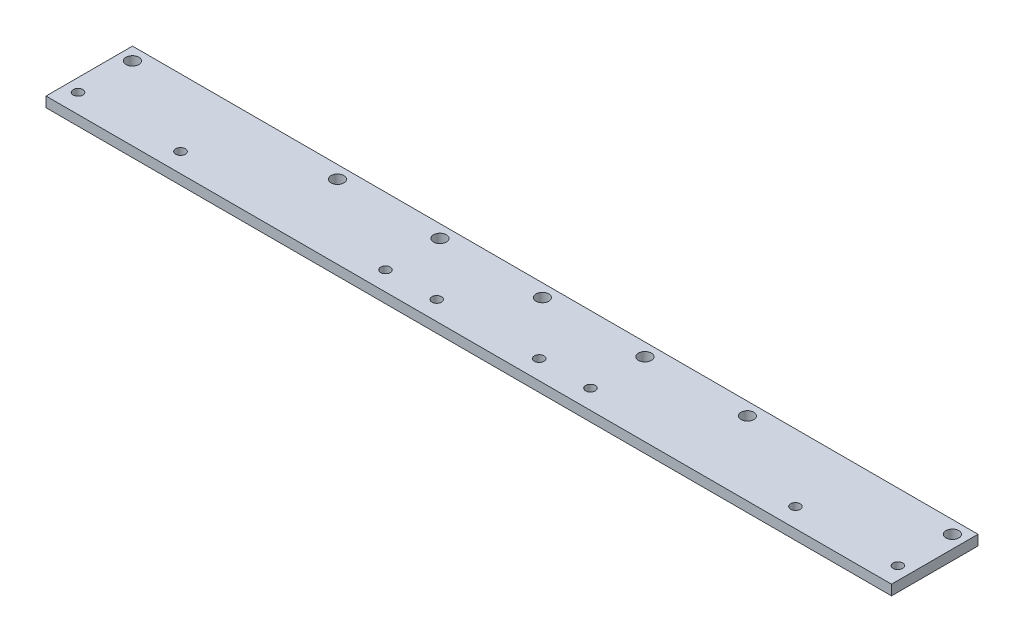
SolidWorks part; units mm, degrees
ref_plane "Front" through (0, 0, 0) normal (0, 0, 1) x (1, 0, 0)
ref_plane "Top" through (0, 0, 0) normal (0, 1, 0) x (1, 0, 0)
ref_plane "Right" through (0, 0, 0) normal (1, 0, 0) x (0, 0, -1)
sketch "Sketch1" plane through (0, 0, 0) normal (0, 1, 0) x (1, 0, 0)
  line L0 (0, 25.5356) -> (0, -1.4644)
  line L3 (0, 25.5356) -> (264, 25.5356)
  line L7 (0, -1.4644) -> (264, -1.4644)
  line L8 (264, -1.4644) -> (264, 25.5356)
  line L9 (264, -1.4644) -> (264, 10.5356)
  line L10 (264, 21.5356) -> (260, 21.5356)
  line L11 (0, 21.5356) -> (4, 21.5356)
  line L12 (4, 21.5356) -> (260, 21.5356)
  line L13 (4, 21.5356) -> (132, 21.5356)
  line L14 (132, 21.5356) -> (260, 21.5356)
  line L15 (264, 10.5356) -> (264, -1.4644)
  line L16 (264, 4.5356) -> (260, 4.5356)
  line L17 (132, 25.5356) -> (132, 23.5356)
  line L18 (4, 21.5356) -> (68, 21.5356)
  line L19 (68, 21.5356) -> (36, 21.5356)
  line L20 (36, 21.5356) -> (36, 4.5356)
  line L21 (196, 21.5356) -> (260, 21.5356)
  line L22 (228, 21.5356) -> (228, 4.5356)
  line L23 (132, 21.5356) -> (132, 4.5356)
  line L24 (132, 21.5356) -> (164, 21.5356)
  circle A0 centre (4, 21.5356) radius 2
  circle A1 centre (260, 21.5356) radius 2
  circle A2 centre (132, 21.5356) radius 2
  circle A3 centre (68, 21.5356) radius 2
  circle A4 centre (196, 21.5356) radius 2
  circle A5 centre (260, 4.5356) radius 1.5
  circle A6 centre (4, 4.5356) radius 1.5
  circle A7 centre (36, 4.5356) radius 1.5
  circle A8 centre (228, 4.5356) radius 1.5
  circle A9 centre (132, 4.5356) radius 1.5
  circle A10 centre (164, 21.5356) radius 2
  circle A11 centre (100, 21.5356) radius 2
  dimension "D5" = 23
  dimension "D6" = 128
  dimension "D9" = 4
  dimension "D10" = 32
  dimension "D1" = 4
  dimension "D2" = 264
  dimension "D3" = 4
  dimension "D4" = 4
  dimension "D7" = 128
  dimension "D8" = 12
extrude "Boss-Extrude1" add sketch "Sketch1" along normal blind 3.175 contours A1 L10 L3 A0 | A1 A0 L10 | A3 L13 A2 L17 L3 L0 L11 A0 | A9 region at (65.9183, 0, -23.5857) region at (1, 0, -18.8856) region at (198.0817, 0, -23.5857)
sketch "Sketch2" plane through (0, 3.175, 0) normal (0, 1, 0) x (1, 0, 0)
  line L0 (37.5, 4.5356) -> (228, 4.5356)
  line L1 (132, 21.5356) -> (132, 4.5356)
  line L2 (132, 4.5356) -> (148, 4.5356)
  line L3 (148, 4.5356) -> (116, 4.5356)
  line L4 (116, 4.5356) -> (100, 4.5356)
  line L5 (148, 4.5356) -> (164, 4.5356)
  circle A0 centre (36, 4.5356) radius 1.5 construction
  circle A1 centre (116, 4.5356) radius 1.5
  circle A2 centre (148, 4.5356) radius 1.5
  circle A3 centre (100, 4.5356) radius 1.5
  circle A4 centre (164, 4.5356) radius 1.5
  dimension "D3" = 16
  dimension "D1" = 16
  dimension "D2" = 16
  dimension "D4" = 16
extrude "Cut-Extrude1" cut sketch "Sketch2" against normal blind 10 contours A3 | A1 | A2 | A4
